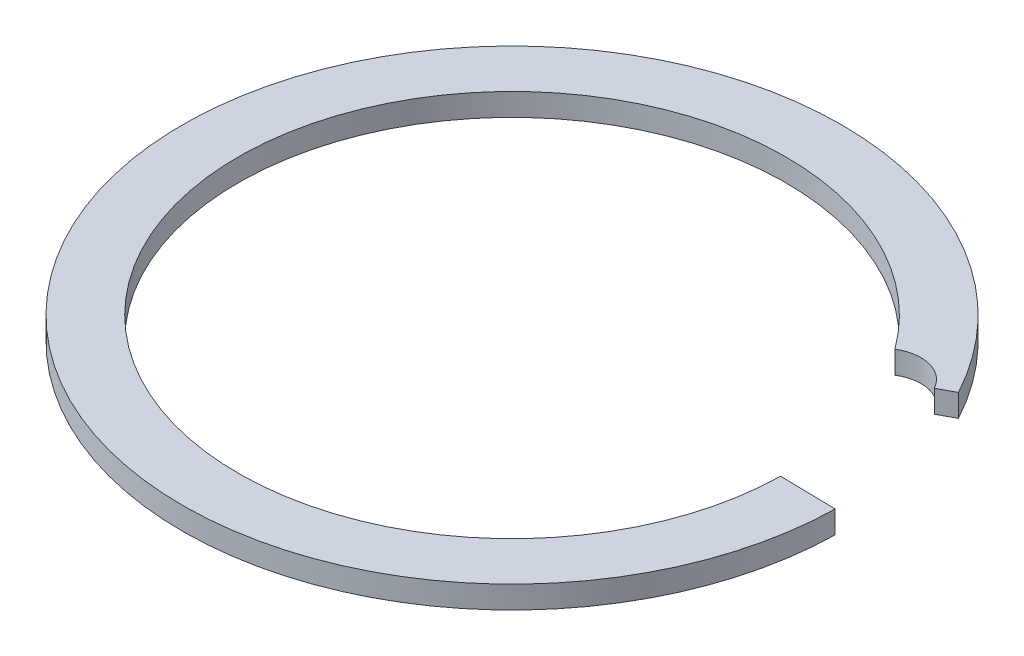
SolidWorks part; units mm, degrees
ref_plane "Front Plane" through (0, 0, 0) normal (0, 0, 1) x (1, 0, 0)
ref_plane "Top Plane" through (0, 0, 0) normal (0, 1, 0) x (1, 0, 0)
ref_plane "Right Plane" through (0, 0, 0) normal (1, 0, 0) x (0, 0, -1)
sketch "Sketch1" plane through (0, 0, 0) normal (0, 1, 0) x (1, 0, 0)
  circle A0 centre (0, 0) radius 10.5 construction
  arc A1 (4.9401, 2.6585) -> (5.609, -0.1082) centre (0, 0) ccw
  dimension "D1" = 21
  dimension "D2" = 5.61
extrude "Extrude-Thin1" add sketch "Sketch1" along normal blind 0.46 thin thin type one direction wall 1.14
sketch "Sketch2" plane through (0, 0, 0) normal (0, 1, 0) x (1, 0, 0)
  circle A0 centre (4.9401, 2.6585) radius 0.7749
extrude "Cut-Extrude1" cut sketch "Sketch2" along normal through all
ref_axis "Axis1" through (0, 0, 0) along (0, 1, 0)
